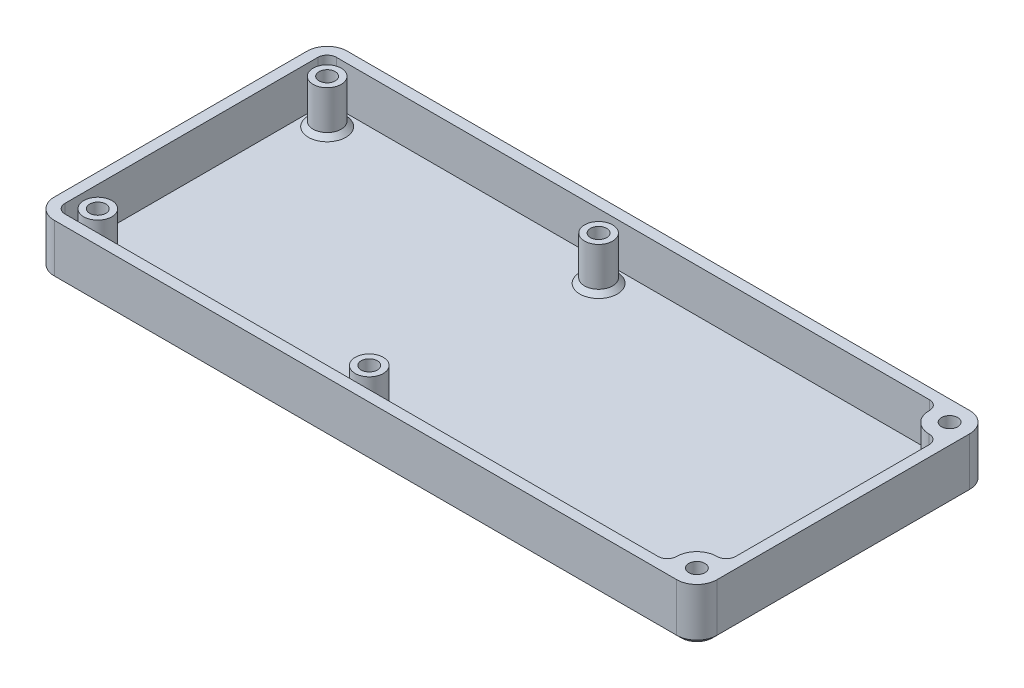
SolidWorks part; units mm, degrees
ref_plane "Front Plane" through (0, 0, 0) normal (0, 0, 1) x (1, 0, 0)
ref_plane "Top Plane" through (0, 0, 0) normal (0, 1, 0) x (1, 0, 0)
ref_plane "Right Plane" through (0, 0, 0) normal (1, 0, 0) x (0, 0, -1)
sketch "Sketch1" plane through (0, 0, 0) normal (0, 1, 0) x (1, 0, 0)
  line L0 (-71.5618, 3.106) -> (63.4382, 3.106) construction
  line L1 (-71.5618, 31.106) -> (63.4382, 31.106)
  line L2 (-71.5618, 31.106) -> (-71.5618, -24.894)
  line L3 (-71.5618, -24.894) -> (63.4382, -24.894)
  line L4 (63.4382, 31.106) -> (63.4382, -24.894)
  line L5 (-60.6618, -24.894) -> (-60.6618, -31.6828) construction
  line L6 (-68.0618, 27.606) -> (-10.0618, 27.606)
  line L7 (-68.0618, 27.606) -> (-68.0618, -21.394)
  line L8 (-68.0618, -21.394) -> (-10.0618, -21.394)
  line L9 (-10.0618, 27.606) -> (-10.0618, -21.394)
  line L10 (-39.5618, -24.894) -> (-39.5618, -31.6828) construction
  line L11 (-18.0618, -24.894) -> (-18.0618, -31.6828) construction
  line L12 (-65.4118, -26.5648) -> (-55.9118, -26.5648) construction
  line L13 (-48.0618, -26.5648) -> (-31.0618, -26.5648) construction
  line L14 (-22.0618, -26.5648) -> (-14.0618, -26.5648) construction
  line L15 (-72.5618, 9.606) -> (-72.5618, -3.394) construction
  line L16 (-71.5618, 3.106) -> (-72.5618, 3.106) construction
  dimension "D1" = 135
  dimension "D2" = 56
  dimension "D3" = 49
  dimension "D4" = 58
  dimension "D5" = 3.5
  dimension "D6" = 3.5
  dimension "D7" = 10.9
  dimension "D8" = 32
  dimension "D9" = 53.5
  dimension "D10" = 2
  dimension "D11" = 13
  dimension "D12" = 9.5
  dimension "D13" = 17
  dimension "D14" = 8
sketch "Sketch3" plane through (0, 0, 0) normal (0, 1, 0) x (1, 0, 0)
  line L4 (66.7382, 34.406) -> (-74.8618, 34.406)
  line L5 (-74.8618, 34.406) -> (-74.8618, -28.194)
  line L6 (-74.8618, -28.194) -> (66.7382, -28.194)
  line L7 (66.7382, -28.194) -> (66.7382, 34.406)
  line L8 (64.4382, 32.106) -> (-72.5618, 32.106)
  line L9 (64.4382, -25.894) -> (64.4382, 32.106)
  line L10 (-72.5618, -25.894) -> (64.4382, -25.894)
  line L11 (-72.5618, 32.106) -> (-72.5618, -25.894)
  line L12 (64.4382, 32.106) -> (-72.5618, 32.106)
  line L13 (64.4382, -25.894) -> (64.4382, 32.106)
  line L14 (-72.5618, -25.894) -> (64.4382, -25.894)
  line L15 (-72.5618, 32.106) -> (-72.5618, -25.894)
  line L16 (-4.0618, 3.106) -> (-4.0618, 34.406) construction
  line L17 (-71.5618, 3.106) -> (63.4382, 3.106) construction
  line L20 (-74.8618, 3.106) -> (52.7382, 3.106) construction
  line L25 (66.7382, -28.194) -> (66.7382, 34.406) construction
  line L26 (64.4382, -25.894) -> (64.4382, 32.106) construction
  dimension "D1" = 1
  dimension "D2" = 2.3
extrude "Boss-Extrude1" add sketch "Sketch3" along normal blind 11.3
sketch "Sketch5" plane through (0, 0, 0) normal (0, 1, 0) x (1, 0, 0)
  line L1 (-72.5618, 32.106) -> (64.4382, 32.106)
  line L2 (-72.5618, 32.106) -> (-72.5618, -25.894)
  line L3 (-72.5618, -25.894) -> (64.4382, -25.894)
  line L4 (64.4382, 32.106) -> (64.4382, -25.894)
extrude "Boss-Extrude2" add sketch "Sketch5" along normal blind 2
sketch "Sketch6" plane through (0, 2, 0) normal (0, 1, 0) x (1, 0, 0)
  circle A0 centre (-68.0618, 27.606) radius 3
  circle A1 centre (-68.0618, -21.394) radius 3
  circle A2 centre (-10.0618, -21.394) radius 3
  circle A3 centre (-10.0618, 27.606) radius 3
extrude "Boss-Extrude3" add sketch "Sketch6" along normal up to surface (9.3 mm away) up to face at (-4.0618, 11.3, -3.106)
fillet "Fillet6" radius 2 1 edges at (64.4382, 6.65, -32.106)
fillet "Fillet8" radius 2 2 edges at (-72.5618, 6.65, 25.894) (-72.5618, 6.65, -32.106)
chamfer "Chamfer1" distance 1 angle 45 4 edges at (-68.0618, 2, 24.394) (-10.0618, 2, 24.394) (-10.0618, 2, -24.606) (-68.0618, 2, -24.606)
sketch "Sketch24" plane through (0, 2, 0) normal (0, 1, 0) x (1, 0, 0)
  line L0 (15.8873, 3.0622) -> (61.5789, 3.0622) construction
  line L2 (66.7382, -28.194) -> (66.7382, 34.406) construction
  circle A0 centre (62.4382, -23.894) radius 4.3
  circle A1 centre (62.4382, 30.0183) radius 4.3
  dimension "D1" = 4.3
extrude "Boss-Extrude7" add sketch "Sketch24" along normal up to surface (9.3 mm away) up to face at (-4.0618, 11.3, -3.106)
fillet "Fillet21" radius 2 1 edges at (58.6317, 6.65, 25.894)
fillet "Fillet22" radius 2 3 edges at (64.4382, 6.65, 20.0874) (64.4382, 6.65, -26.2118) (58.679, 6.65, -32.106)
fillet "Fillet20" radius 4.3 4 edges at (66.7382, 5.65, 28.194) (-74.8618, 5.65, -34.406) (-74.8618, 5.65, 28.194) (66.7382, 5.65, -34.406)
hole_wizard "CSK for #4 Flat Head Socket Cap Screw1" positions "Sketch28" profile "Sketch27" countersink size "#4" standard "ANSI Inch"
sketch "Sketch28" plane through (0, 0, 0) normal (0, -1, 0) x (-1, 0, 0)
  point P0 (68.0618, 27.606)
  point P4 (68.0618, -21.394)
  point P8 (-62.4382, 30.106)
  point P12 (-62.4382, -23.894)
  point P15 (10.0618, -21.394)
  point P19 (10.0618, 27.606)
sketch "Sketch27" plane through (-68.0618, 0, -27.606) normal (1, 0, 0) x (0, 0, -1)
  line L0 (0, 0) -> (0, 15.0378)
  line L1 (0, 15.0378) -> (1.7272, 14)
  line L2 (1.7272, 14) -> (1.7272, 1.8805)
  line L3 (1.7272, 1.8805) -> (3.3619, 0)
  line L5 (3.3619, 0) -> (0, 0)
  line L6 (-1.7272, 1.8805) -> (-3.3619, 0) construction
  line L10 (0, 15.0378) -> (-1.7272, 14) construction
  line L11 (0, -6.35) -> (0, 107.95) construction
  dimension "Hole Dia." = 3.4544
  dimension "Hole Depth" = 14
  dimension "Near C'Sink Dia." = 6.7238
  dimension "Near C'Sink Angle" = 82
  dimension "Drill Angle" = 118
chamfer "Chamfer7" distance 1 angle 45 8 edges at (-74.8618, 0, -3.106) (-73.6023, 0, 26.9346) (-73.6023, 0, -33.1466) (-4.0618, 0, 28.194) (-4.0618, 0, -34.406) (65.4788, 0, 26.9346) (65.4788, 0, -33.1466) (66.7382, 0, -3.106)
